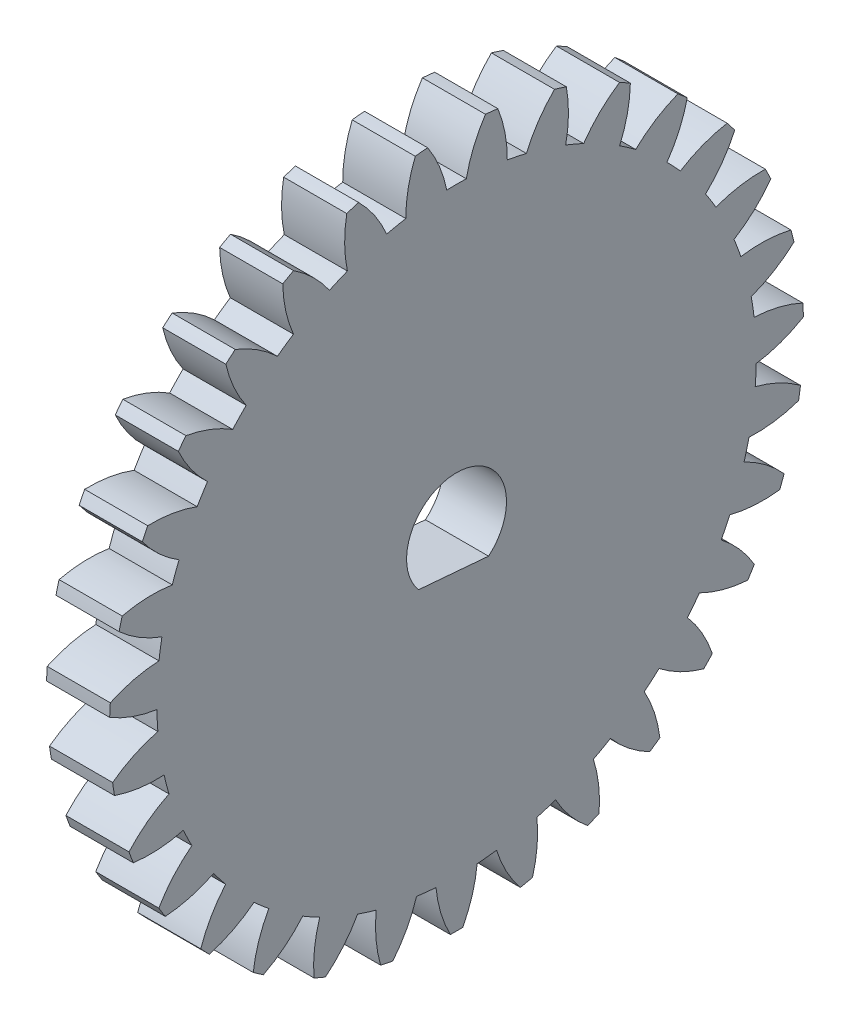
SolidWorks part; units mm, degrees
ref_plane "Plane1" through (0, 0, 0) normal (0, 0, 1) x (1, 0, 0)
ref_plane "Plane2" through (0, 0, 0) normal (0, 1, 0) x (1, 0, 0)
ref_plane "Plane3" through (0, 0, 0) normal (1, 0, 0) x (0, 0, -1)
sketch "HoldingSke" plane through (0, 0, 0) normal (0, 1, 0) x (1, 0, 0)
  line L0 (0, 0) -> (0.8572, -0.515)
  line L1 (-15, 0) -> (100, 0) construction
  line L2 (0, 0) -> (-2.1039, 2.3779)
  line L3 (0, 0) -> (-11.863, 4.5341)
  line L4 (0, 0) -> (7.4025, 4.4479)
  line L5 (0, 0) -> (-46.8476, -17.4728)
  line L6 (0, 0) -> (-1.6579, -1.1186)
  line L7 (-2.1039, 2.3779) -> (8.6586, 51.2059)
  line L8 (-76.2, 54.61) -> (-76.1, 54.61)
  line L9 (-71.009, 38.7566) -> (-53.1078, 45.2721)
  line L10 (-76.2, 71.12) -> (104.1128, 71.12)
  line L11 (0, 0) -> (-2, 0)
  line L12 (-76.2, 101.6) -> (-76.162, 101.6)
  line L13 (24.9733, 27.94) -> (52.9518, 28.4284)
  line L14 (24.9733, 27.94) -> (24.9743, 27.94)
  line L15 (24.9733, 27.94) -> (100.4006, 29.5858)
  line L16 (-63.627, -1) -> (-12.827, -1)
  circle A0 centre (0, 0) radius 0.5
  circle A1 centre (0, 0) radius 14.249
  circle A2 centre (0, 0) radius 37.5
  circle A3 centre (0, 0) radius 0.5
  dimension "MHD" = 28.498
  dimension "Hub_dia" = 75
  dimension "Bore" = 1
  dimension "MBD" = 1
  dimension "Num_teeth" = 31
  dimension "Pitch" = 1
  dimension "Overall_len" = 50
  dimension "Show_teeth" = 31
  dimension "Thickness" = 2
  dimension "OAL" = 50.0001
  dimension "T_dim" = 0.1
  dimension "Ap" = 20
  dimension "H" = 19.05
  dimension "Pitch_radius" = 180.3128
  dimension "Width" = 2
  dimension "Backlash" = 0.038
  dimension "Addendum_fac" = 1
  dimension "Dedendum_fac" = 1.25
  dimension "Clearance_fac" = 0.25
  dimension "Dedendum_add" = 0.001
  dimension "Module" = 1
sketch "BasProSke" plane through (0, 0, 0) normal (0, 1, 0) x (1, 0, 0)
  line L0 (-10, 0) -> (60, 0) construction
  line L1 (0, 0) -> (0, 16.5)
  line L2 (0, 0) -> (2, 0)
  line L3 (2, 0) -> (2, 16.5)
  line L4 (2, 16.5) -> (0, 16.5)
  dimension "Thickness" = 2
  dimension "Diameter" = 33
revolve "Base-Revolve" add sketch "BasProSke" angle 360 about L0
sketch "TooCutSke" plane through (0, 0, 0) normal (1, 0, 0) x (0, 0, -1)
  line L1 (0, 0) -> (0, 107) construction
  line L2 (0, 0) -> (-0.8515, 15.4766) construction
  line L3 (0, 0) -> (-3.1328, 30.8078) construction
  line L4 (-0.8515, 15.4766) -> (-1.5664, 15.4039) construction
  arc A0 (0.4642, 14.2414) -> (-0.4642, 14.2414) centre (0, 0) ccw
  arc A1 (1.3919, 16.4667) -> (-1.3919, 16.4667) centre (0, 0) ccw
  circle A2 centre (0, 0) radius 15.5 construction
  circle A3 centre (0, 0) radius 14.5652 construction
  arc A4 (-0.4642, 14.2414) -> (-1.3919, 16.4667) centre (-6.5414, 13.0137) ccw
  arc A5 (1.3919, 16.4667) -> (0.4642, 14.2414) centre (6.5414, 13.0137) ccw
  dimension "Root_dia" = 28.498
  dimension "Overcut_dia" = 33.0508
  dimension "Pitch_dia" = 31
  dimension "Base_dia" = 29.1305
  dimension "Flank_rad" = 6.2
  dimension "Half_ang" = 5.806
  dimension "Half_CT" = 0.7186
extrude "ToothCut" cut sketch "TooCutSke" along normal through all
fillet "Breaks" [suppressed] radius 0.02 tangent propagation no
fillet "RootFillets" [suppressed] radius 0.251
pattern_circular "TeethCuts" count 31 every 11.613 about axis through (-10, 0, 0) along (1, 0, 0) of "ToothCut", "RootFillets", "Breaks"
sketch "HubNeaOneSke" plane through (0, 0, 0) normal (-1, 0, 0) x (0, 0, 1)
  circle A0 centre (0, 0) radius 14.249
  dimension "Diameter" = 28.498
extrude "HubNearOne" [suppressed] add sketch "HubNeaOneSke" along normal blind 48.0001
sketch "HubNeaBotSke" plane through (0, 0, 0) normal (-1, 0, 0) x (0, 0, 1)
  circle A0 centre (0, 0) radius 14.249
  dimension "Diameter" = 28.498
extrude "HubNearBoth" [suppressed] add sketch "HubNeaBotSke" along normal blind 24
ref_plane "FarPln" through (2, 0, 0) normal (1, 0, 0) x (0, 0, -1)
sketch "HubFarSke" plane through (2, 0, 0) normal (1, 0, 0) x (0, 0, -1)
  circle A0 centre (0, 0) radius 14.249
  dimension "Diameter" = 28.498
extrude "HubFar" [suppressed] add sketch "HubFarSke" along normal blind 24
sketch "BorSke" plane through (0, 0, 0) normal (1, 0, 0) x (0, 0, -1)
  line L0 (-1.806, -1.5423) -> (1.5211, -1.824)
  arc A0 (-1.806, -1.5423) -> (1.5211, -1.824) centre (0, 0) cw
extrude "Bore" cut sketch "BorSke" along normal mid plane 100.0001
sketch "KeySke" plane through (0, 0, 0) normal (1, 0, 0) x (0, 0, -1)
  line L0 (-0.05, 0) -> (-0.05, 0.6)
  line L1 (-0.05, 0.6) -> (0.05, 0.6)
  line L2 (0.05, 0.6) -> (0.05, 0)
  line L3 (0, 0) -> (0, 34) construction
  line L4 (-0.05, 0) -> (0.05, 0)
  dimension "Offset" = 0.6
extrude "Keyway" [suppressed] cut sketch "KeySke" along normal mid plane 100.0001
pattern_circular "Keyway2" [suppressed] count 2 every 90 about axis through (-10, 0, 0) along (1, 0, 0) reverse direction yes
scale "Scale1" scale about centroid uniform scaling no x scale factor 1.5 y scale factor 1 z scale factor 1
equation "' \"Module@HoldingSke\" = 6.35"
equation "' \"Num_teeth@HoldingSke\" = 12"
equation "' \"Ap@HoldingSke\" =  20"
equation "' \"Ap@HoldingSke\" = 20"
equation "' \"Width@HoldingSke\" = 0.5 * 25.4"
equation "' \"Hub_dia@HoldingSke\"= 1 * 25.4"
equation "' \"Hub_dia@HoldingSke\" = 1 * 25.4"
equation "' \"Overall_len@HoldingSke\" = 1.0 * 25.4"
equation "' \"Bore@HoldingSke\" = 0.75 * 25.4"
equation "' \"T_dim@HoldingSke\" = 0.1 * 25.4"
equation "' \"Width@KeySke\" = 0.25 * 25.4"
equation "' \"Show_teeth@HoldingSke\" = 13"
equation "' \"Backlash@HoldingSke\" = 0.009 * 25.4"
equation "' \"Addendum_fac@HoldingSke\" = 1.0"
equation "' \"Dedendum_fac@HoldingSke\" = 1.25"
equation "' \"Dedendum_add@HoldingSke\" = 0.00005 * 25.4"
equation "' \"Clearance_fac@HoldingSke\" = 0.25"
equation "\"Pitch@HoldingSke\" = 1 / \"Module@HoldingSke\""
equation "\"Overcut_dia@TooCutSke\" = (\"Num_teeth@HoldingSke\" + 2 * \"Addendum_fac@HoldingSke\") / \"Pitch@HoldingSke\" + 0.002 * 25.4"
equation "\"Pitch_dia@TooCutSke\" = \"Num_teeth@HoldingSke\" / \"Pitch@HoldingSke\""
equation "\"Base_dia@TooCutSke\" = \"Num_teeth@HoldingSke\" / \"Pitch@HoldingSke\" * cos((\"Ap@HoldingSke\"  * 3.14159265 / 180))"
equation "\"Root_dia@TooCutSke\" = (\"Num_teeth@HoldingSke\" + 2) / \"Pitch@HoldingSke\" - 2 * (\"Addendum_fac@HoldingSke\" + \"Dedendum_fac@HoldingSke\") / \"Pitch@HoldingSke\" - \"Dedendum_add@HoldingSke\" * 2"
equation "\"Half_ang@TooCutSke\" = 180 / \"Num_teeth@HoldingSke\""
equation "\"Half_CT@TooCutSke\" = \"Num_teeth@HoldingSke\" / \"Pitch@HoldingSke\" * sin((3.14159265 / 2 / \"Num_teeth@HoldingSke\")) / 2 - 7 * \"Backlash@HoldingSke\" / 4"
equation "\"Flank_rad@TooCutSke\" = \"Num_teeth@HoldingSke\" / \"Pitch@HoldingSke\" / 5"
equation "\"Radius@RootFillets\" = \"Clearance_fac@HoldingSke\" / \"Pitch@HoldingSke\" + \"Dedendum_add@HoldingSke\""
equation "\"Break_rad@Breaks\" = 0.02 / \"Pitch@HoldingSke\""
equation "\"Thickness@HoldingSke\" = \"Width@HoldingSke\""
equation "\"OAL@HoldingSke\" = \"Thickness@HoldingSke\""
equation "\"MHD@HoldingSke\" = (\"Num_teeth@HoldingSke\" + 2) / \"Pitch@HoldingSke\" - 2 * (\"Addendum_fac@HoldingSke\" + \"Dedendum_fac@HoldingSke\")  / \"Pitch@HoldingSke\" - \"Dedendum_add@HoldingSke\" * 2"
equation "\"MBD@HoldingSke\" = (\"Num_teeth@HoldingSke\" + 2) / \"Pitch@HoldingSke\" - 2 * (\"Addendum_fac@HoldingSke\" + \"Dedendum_fac@HoldingSke\")  / \"Pitch@HoldingSke\" - \"Dedendum_add@HoldingSke\" * 2 - 0.002 * 25.4"
equation "\"MHD@HoldingSke\" = ((sgn( \"MHD@HoldingSke\" - \"Hub_dia@HoldingSke\" )-1)*( \"MHD@HoldingSke\" - \"Hub_dia@HoldingSke\" ))/-2+ \"Hub_dia@HoldingSke\""
equation "\"MBD@HoldingSke\" = ((sgn( \"MBD@HoldingSke\" - \"Bore@HoldingSke\" )-1)*( \"MBD@HoldingSke\" - \"Bore@HoldingSke\" ))/-2+ \"Bore@HoldingSke\""
equation "\"OAL@HoldingSke\" = ((sgn( \"OAL@HoldingSke\" - \"Overall_len@HoldingSke\" )+1)*( \"OAL@HoldingSke\" - \"Overall_len@HoldingSke\" ))/2 + \"Overall_len@HoldingSke\" + 0.000002 * 25.4"
equation "\"Num_teeth@TeethCuts\" = int( \"Show_teeth@HoldingSke\" ) + 1"
equation "\"Num_teeth@TeethCuts\" = ((sgn( \"Num_teeth@TeethCuts\" - \"Num_teeth@HoldingSke\" )-1)*( \"Num_teeth@TeethCuts\" - \"Num_teeth@HoldingSke\" ))/-2+ \"Num_teeth@HoldingSke\""
equation "\"Num_teeth@TeethCuts\" = ((sgn( \"Num_teeth@TeethCuts\" - 2.0)+1)*( \"Num_teeth@TeethCuts\" - 2.0))/2 +2.0"
equation "\"Angle@TeethCuts\" = 360.0 / \"Num_teeth@HoldingSke\""
equation "\"Diameter@BasProSke\" = (\"Num_teeth@HoldingSke\" + 2 * \"Addendum_fac@HoldingSke\") / \"Pitch@HoldingSke\""
equation "\"Thickness@BasProSke\"  = \"Thickness@HoldingSke\""
equation "' \"Fillet_rad@BasProSke\" =  \"Thickness@HoldingSke\" * 0.05"
equation "' \"Fillet_rad@BasProSke\" = \"Thickness@HoldingSke\" * 0.05"
equation "\"MHD@HoldingSke\" = ((sgn( \"MHD@HoldingSke\" - \"Root_dia@TooCutSke\" )-1)*( \"MHD@HoldingSke\" - \"Root_dia@TooCutSke\" ))/-2+ \"Root_dia@TooCutSke\""
equation "\"Diameter@HubNeaOneSke\" = \"MHD@HoldingSke\""
equation "\"Length@HubNearOne\" = \"OAL@HoldingSke\" - \"Thickness@BasProSke\""
equation "\"Diameter@HubNeaBotSke\" = \"MHD@HoldingSke\""
equation "\"Length@HubNearBoth\" = ( \"OAL@HoldingSke\" - \"Thickness@BasProSke\" ) / 2.0"
equation "\"Thickness@FarPln\" = \"Thickness@BasProSke\""
equation "\"Diameter@HubFarSke\" = \"MHD@HoldingSke\""
equation "\"Length@HubFar\" = ( \"OAL@HoldingSke\" - \"Thickness@BasProSke\" ) / 2.0"
equation "\"D1@Bore\" = \"OAL@HoldingSke\" * 2.0"
equation "\"D1@Keyway\" = \"OAL@HoldingSke\" * 2.0"
equation "\"Offset@KeySke\" = \"T_dim@HoldingSke\" + \"MBD@HoldingSke\" / 2.0"
